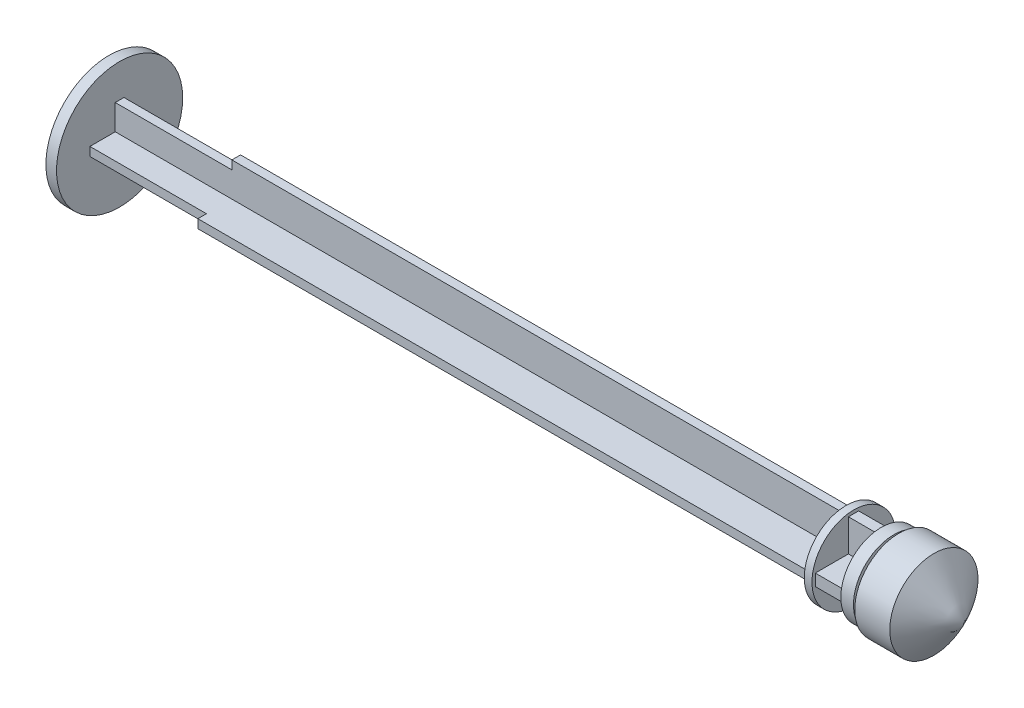
SolidWorks part; units mm, degrees
ref_plane "Front Plane" through (0, 0, 0) normal (0, 0, 1) x (1, 0, 0)
ref_plane "Top Plane" through (0, 0, 0) normal (0, 1, 0) x (1, 0, 0)
ref_plane "Right Plane" through (0, 0, 0) normal (1, 0, 0) x (0, 0, -1)
sketch "Sketch1" plane through (0, 0, 0) normal (1, 0, 0) x (0, 0, -1)
  circle A0 centre (0, 0) radius 6.235
  dimension "D1" = 12.47
extrude "Boss-Extrude1" add sketch "Sketch1" along normal blind 1.05
sketch "Sketch2" plane through (1.05, 0, 0) normal (1, 0, 0) x (0, 0, -1)
  line L1 (-2.935, -0.43) -> (2.935, -0.43)
  line L2 (-2.935, -0.43) -> (-2.935, 0.43)
  line L3 (-2.935, 0.43) -> (2.935, 0.43)
  line L4 (2.935, -0.43) -> (2.935, 0.43)
  line L5 (-0.43, 2.935) -> (0.43, 2.935)
  line L6 (-0.43, 2.935) -> (-0.43, -2.935)
  line L7 (-0.43, -2.935) -> (0.43, -2.935)
  line L8 (0.43, 2.935) -> (0.43, -2.935)
  dimension "D1" = 0.43
  dimension "D2" = 0.86
  dimension "D3" = 0.43
  dimension "D4" = 0.86
  dimension "D5" = 2.935
  dimension "D6" = 2.935
  dimension "D7" = 2.935
  dimension "D8" = 2.935
extrude "Boss-Extrude5" add sketch "Sketch2" along normal blind 11.52 contours L8 L5 L6 L3 | L8 L1 L6 L7 | L3 L4 L1 L2 region at (1.05, -1.6825, 0) region at (1.05, 1.6825, 0)
sketch "Sketch10" plane through (12.57, 0, 0) normal (1, 0, 0) x (0, 0, -1)
  line L0 (-0.43, 2.935) -> (-0.43, 0.43) construction
  line L1 (-0.43, 3.785) -> (0.43, 3.785)
  line L2 (-0.43, 3.785) -> (-0.43, -3.785)
  line L3 (-0.43, -3.785) -> (0.43, -3.785)
  line L4 (0.43, 3.785) -> (0.43, -3.785)
  line L5 (0.43, -0.43) -> (0.43, -2.935) construction
  dimension "D1" = 7.57
  dimension "D2" = 3.785
extrude "Boss-Extrude6" add sketch "Sketch10" along normal blind 60.27
sketch "Sketch11" plane through (12.57, 0, 0) normal (1, 0, 0) x (0, 0, -1)
  line L0 (-2.935, 0.43) -> (-0.43, 0.43) construction
  line L1 (-3.785, 0.43) -> (3.785, 0.43)
  line L2 (-3.785, 0.43) -> (-3.785, -0.43)
  line L3 (-3.785, -0.43) -> (3.785, -0.43)
  line L4 (3.785, 0.43) -> (3.785, -0.43)
  line L5 (0.43, -0.43) -> (2.935, -0.43) construction
  dimension "D1" = 7.57
  dimension "D2" = 3.785
extrude "Boss-Extrude8" add sketch "Sketch11" along normal blind 60.27
sketch "Sketch15" plane through (72.84, 0, 0) normal (1, 0, 0) x (0, 0, -1)
  circle A0 centre (0, 0) radius 4.13
extrude "Boss-Extrude9" add sketch "Sketch15" along normal blind 0.76
sketch "Sketch16" plane through (73.6, 0, 0) normal (1, 0, 0) x (0, 0, -1)
  line L1 (-0.5235, 3.8) -> (0.4868, 3.8)
  line L2 (-0.5235, 3.8) -> (-0.5235, -3.8)
  line L3 (-0.5235, -3.8) -> (0.4868, -3.8)
  line L4 (0.4868, 3.8) -> (0.4868, -3.8)
  line L5 (-3.8, 0.6246) -> (3.8, 0.6246)
  line L6 (-3.8, 0.6246) -> (-3.8, -0.5327)
  line L7 (-3.8, -0.5327) -> (3.8, -0.5327)
  line L8 (3.8, 0.6246) -> (3.8, -0.5327)
  dimension "D1" = 7.6
  dimension "D2" = 7.6
  dimension "D3" = 3.8
  dimension "D4" = 3.8
extrude "Boss-Extrude10" add sketch "Sketch16" along normal blind 2.71 contours L8 L5 L4 L7 | L2 L5 L4 L1 | L5 L8 L7 L6 | L4 L3 L2 L1 region at (73.6, 2.2123, 0.0184) region at (73.6, 0.0459, -2.1434)
sketch "Sketch17" plane through (76.31, 0, 0) normal (1, 0, 0) x (0, 0, -1)
  circle A0 centre (0, 0) radius 3.99
extrude "Boss-Extrude11" add sketch "Sketch17" along normal blind 1.25
sketch "Sketch18" plane through (77.56, 0, 0) normal (1, 0, 0) x (0, 0, -1)
  line L1 (-0.45, 2.63) -> (0.45, 2.63)
  line L2 (-0.45, 2.63) -> (-0.45, -2.63)
  line L3 (-0.45, -2.63) -> (0.45, -2.63)
  line L4 (0.45, 2.63) -> (0.45, -2.63)
  line L5 (-2.63, 0.45) -> (2.63, 0.45)
  line L6 (-2.63, 0.45) -> (-2.63, -0.45)
  line L7 (-2.63, -0.45) -> (2.63, -0.45)
  line L8 (2.63, 0.45) -> (2.63, -0.45)
  dimension "D1" = 5.26
  dimension "D2" = 5.26
  dimension "D3" = 0.9
  dimension "D4" = 0.9
  dimension "D5" = 0.45
  dimension "D6" = 0.45
  dimension "D7" = 2.63
  dimension "D8" = 2.63
extrude "Boss-Extrude13" add sketch "Sketch18" along normal blind 0.5 contours L8 L5 L4 L7 | L2 L5 L4 L1 | L6 L7 L2 L5 | L2 L7 L4 L5 | L7 L2 L3 L4 region at (77.56, 1.54, 0) region at (77.56, 0, 0) region at (77.56, 0, 1.54) region at (77.56, 0, -1.54) region at (77.56, -1.54, 0)
sketch "Sketch19" plane through (78.06, 0, 0) normal (1, 0, 0) x (0, 0, -1)
  circle A0 centre (0, 0) radius 4.36
extrude "Boss-Extrude14" add sketch "Sketch19" along normal blind 3.46
sketch "Sketch20" plane through (81.52, 0, 0) normal (1, 0, 0) x (0, 0, -1)
  circle A0 centre (0, 0) radius 4.36
extrude "Boss-Extrude15" add sketch "Sketch20" along normal blind 3.46 draft 55
